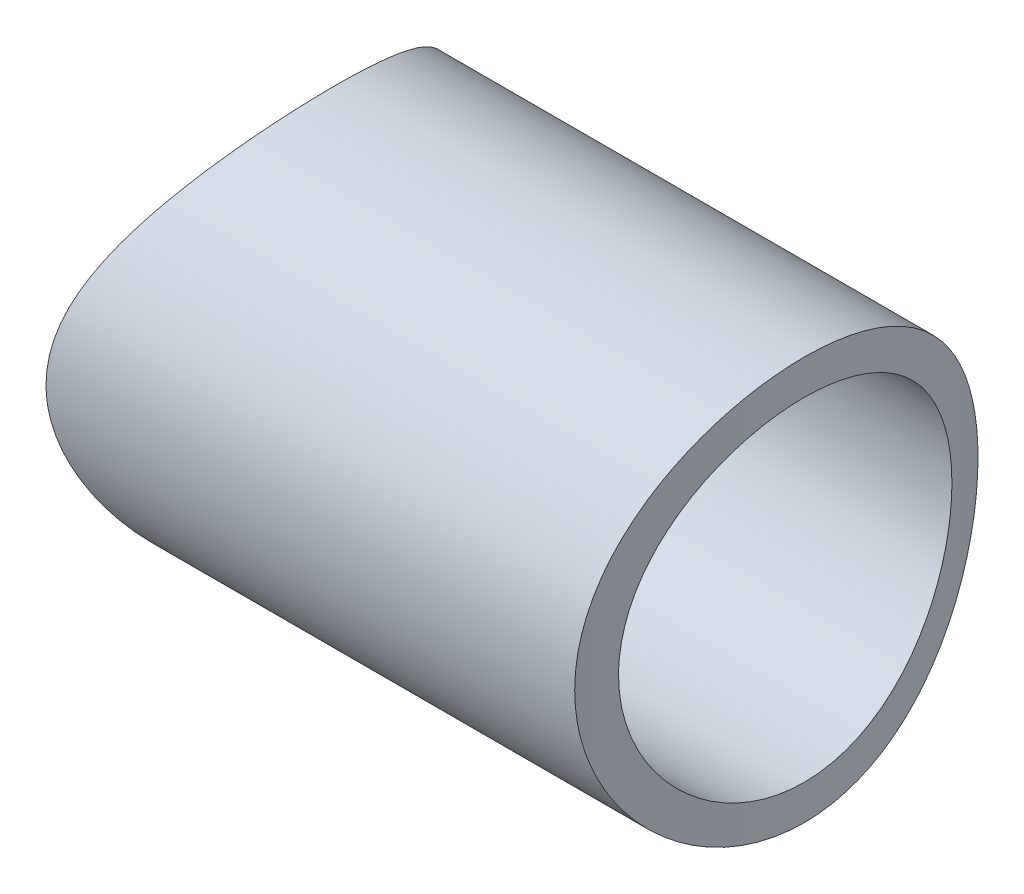
SolidWorks part; units mm, degrees
material "PTFE (general)"
ref_plane "Front Plane" through (0, 0, 0) normal (0, 0, 1) x (1, 0, 0)
ref_plane "Top Plane" through (0, 0, 0) normal (0, 1, 0) x (1, 0, 0)
ref_plane "Right Plane" through (0, 0, 0) normal (1, 0, 0) x (0, 0, -1)
sketch "Sketch1" plane through (0, 0, 0) normal (0, 1, 0) x (1, 0, 0)
  circle A0 centre (0, 0) radius 42.725
  circle A1 centre (0, 0) radius 15.875
  dimension "D1" = 31.75
  dimension "D2" = 85.45
extrude "Boss-Extrude1" add sketch "Sketch1" along normal blind 1
sketch "Sketch2" plane through (0, 1, 0) normal (0, 1, 0) x (1, 0, 0)
  circle A0 centre (0, 0) radius 16.875
  circle A1 centre (0, 0) radius 15.875
  circle A2 centre (0, 0) radius 42.725
  circle A3 centre (0, 0) radius 41.725
  circle A4 centre (0, 0) radius 15.875 construction
  circle A5 centre (0, 0) radius 42.725 construction
  dimension "D1" = 0
  dimension "D2" = 1
  dimension "D3" = 0
  dimension "D4" = 1
extrude "Boss-Extrude2" add sketch "Sketch2" along normal blind 25 contours A2 | A1 | A0 | A3
sketch "Sketch3" plane through (0, 0, 0) normal (1, 0, 0) x (0, 0, -1)
  line L1 (-42.725, 0) -> (42.725, 0) construction
  circle A1 centre (0, 11) radius 9.53
  dimension "D1" = 11
  dimension "D2" = 19.06
extrude "Cut-Extrude1" cut sketch "Sketch3" along normal through all
sketch "Sketch9" plane through (0, 0, 0) normal (1, 0, 0) x (0, 0, -1)
  circle A0 centre (0, 11) radius 11.53
  circle A1 centre (0, 11) radius 9.53
  dimension "D1" = 2
  dimension "D2" = 19.06
extrude "Boss-Extrude3" add sketch "Sketch9" along normal up to surface (41.1398 mm away) up to face at (0, 0, 42.725)
sketch "Sketch10" plane through (0, 26, 0) normal (0, 1, 0) x (1, 0, 0)
  line L5 (0, 11.53) -> (0, -11.53) construction
  line L10 (1.5624, 15.7979) -> (41.0361, 11.894)
  line L11 (1.5624, -15.7979) -> (41.0361, -11.894)
  circle A3 centre (0, 0) radius 15.875 construction
  circle A4 centre (0, 0) radius 15.875
  circle A5 centre (0, 0) radius 42.725
  circle A6 centre (0, 0) radius 42.725 construction
  circle M1 centre (0, 0) radius 16.875
  circle M2 centre (0, 0) radius 15.875
  dimension "D2" = 0
  dimension "D1" = 0
extrude "Cut-Extrude2" cut sketch "Sketch10" against normal through all both and the other way through all contours M2 | L11 L10 M2 M1 | L10 A5 L11 M1 | A4 region at (-16.2899, 26, 0) region at (0, 26, 0) region at (-18.0716, 26, 0)
sketch "Sketch11" plane through (0, 0, 0) normal (1, 0, 0) x (0, 0, -1)
  circle A0 centre (0, 11) radius 11.53
  circle A1 centre (0, 11) radius 9.53 construction
  circle A2 centre (0, 11) radius 50
  dimension "D1" = 2
  dimension "D2" = 100
extrude "Cut-Extrude4" cut sketch "Sketch11" along normal through all both and the other way through all
